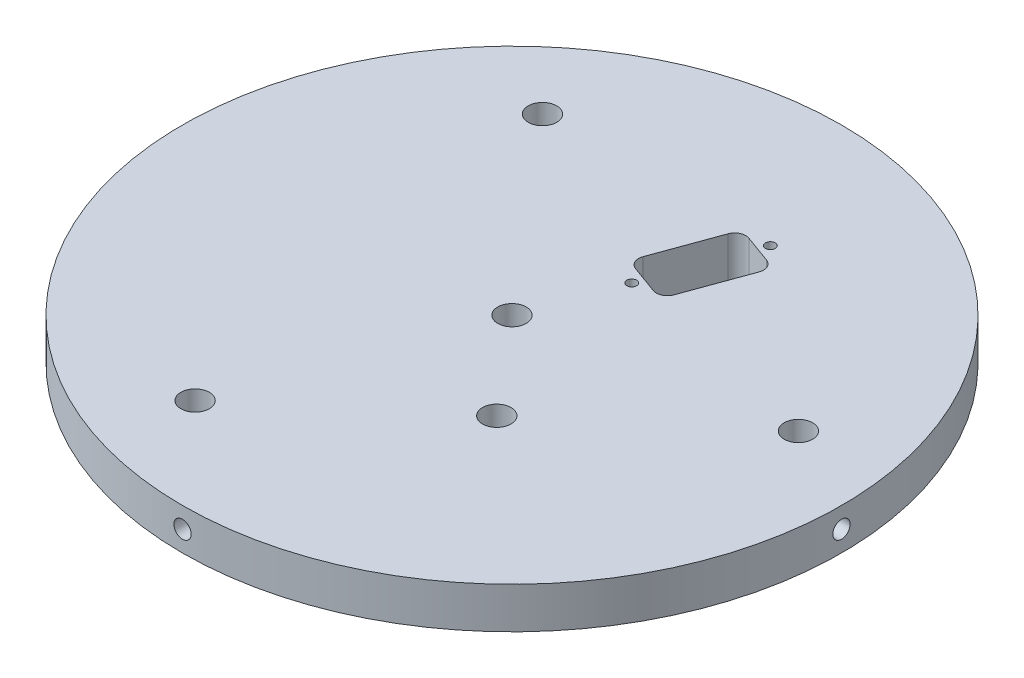
SolidWorks part; units mm, degrees
material "6061-T6 (SS)"
ref_plane "Front Plane" through (0, 0, 0) normal (0, 0, 1) x (1, 0, 0)
ref_plane "Top Plane" through (0, 0, 0) normal (0, 1, 0) x (1, 0, 0)
ref_plane "Right Plane" through (0, 0, 0) normal (1, 0, 0) x (0, 0, -1)
sketch "Sketch1" plane through (0, 0, 0) normal (0, 1, 0) x (1, 0, 0)
  line L0 (0, 0) -> (-50.3682, 60.0265)
  line L1 (0, 0) -> (50.3682, 60.0265)
  line L2 (0, 0) -> (0, 72.1431) construction
  circle A0 centre (0, 0) radius 78.359
  circle A1 centre (0, 0) radius 76.1746
  circle A2 centre (0, 0) radius 76.1746
  dimension "D1" = 156.718
  dimension "D2" = 152.3492
  dimension "D3" = 152.3492
  dimension "D4" = 80
extrude "Boss-Extrude1" add sketch "Sketch1" along normal blind 25.4 contours L2 A2 L1 A0 | L2 A1 L1 A2 | L2 A2 L1 A1 | L2 A0 L1 A2 | A2 L2 A1 L0 | A0 L2 A2 L0 | A2 L2 A0 L0 | A1 L2 A2 L0 region at (0, 0, 13.3592) region at (-23.5316, 0, -29.974) region at (-33.0764, 0, 70.9325) region at (-48.8794, 0, -59.85)
ref_plane "Plane1" through (0, 12.7, 0) normal (0, 1, 0) x (1, 0, 0)
sketch "Sketch6" plane through (0, 25.4, 0) normal (0, 1, 0) x (1, 0, 0)
  circle A0 centre (0, 0) radius 76.1746
  dimension "D1" = 152.3492
extrude "Boss-Extrude5" add sketch "Sketch6" along normal blind 9.525
sketch "Sketch7" plane through (0, 0, 0) normal (0, -1, 0) x (1, 0, 0)
  circle A0 centre (0, 0) radius 76.1746
  dimension "D1" = 152.3492
extrude "Boss-Extrude6" add sketch "Sketch7" along normal blind 9.525
sketch "Sketch8" plane through (0, -9.525, 0) normal (0, -1, 0) x (1, 0, 0)
  circle A0 centre (0, 0) radius 73.025
  dimension "D1" = 146.05
extrude "Cut-Extrude5" cut sketch "Sketch8" against normal up to surface (34.925 mm away) up to face at (0, 25.4, 76.1746)
ref_plane "Plane2" through (0, 0, -76.1746) normal (0, 0, -1) x (-1, 0, 0)
ref_plane "Plane5" through (0, 25.4, 0) normal (0, 1, 0) x (1, 0, 0)
ref_axis "Axis1" through (0, 0, 0) along (0, 1, 0)
sketch "Sketch3" plane through (0, 0, -76.1746) normal (0, 0, -1) x (-1, 0, 0)
  line L4 (76.1746, 0) -> (-76.1746, 0)
  line L5 (-76.1746, -9.525) -> (76.1746, -9.525)
  line L6 (76.1746, 25.4) -> (-76.1746, 25.4)
  line L7 (76.1746, 34.925) -> (-76.1746, 34.925)
  line L8 (0, 34.925) -> (0, 25.4) construction
  line L9 (0, 0) -> (0, -9.525) construction
  circle A0 centre (0, 30.1625) radius 2
  circle A1 centre (0, -4.7625) radius 2
  point P12 (0, 30.1625)
  point P13 (0, -4.7625)
  point P14 (-77.5445, 179.1871)
  dimension "D1" = 4
extrude "Cut-Extrude2" cut sketch "Sketch3" against normal blind 9.525 contours L8 A0 | L8 A0 | L9 A1 | L9 A1 region at (0, 30.1625, -76.1746) region at (0, -4.7625, -76.1746)
extrude "Cut-Extrude3" cut sketch "Sketch1<7>" against normal blind 9.525 from surface contours L2 A1 L1 A2 | A1 L2 A2 L0 | A2 L2 A0 L0 | L2 A2 L1 A0 region at (-23.5316, 0, -29.974) region at (-48.8794, 0, -59.85) starting at plane "Plane5"
sketch "Sketch1<7>" plane through (0, 0, 0) normal (0, 1, 0) x (1, 0, 0) same geometry as "Sketch1"
pattern_circular "CirPattern2" count 3 over 360 about axis through (0, 0, 0) along (0, 1, 0) of "Cut-Extrude3"
ref_plane "Plane3" through (0, 34.925, 0) normal (0, 1, 0) x (1, 0, 0)
sketch "Sketch4" plane through (0, 34.925, 0) normal (0, 1, 0) x (1, 0, 0)
  circle A0 centre (0, 0) radius 73.025
  dimension "D1" = 146.05
extrude "Boss-Extrude4" add sketch "Sketch4" against normal blind 9.525
pattern_circular "CirPattern3" count 4 over 360 about axis through (0, 0, 0) along (0, 1, 0) of "Cut-Extrude2"
sketch "Sketch9" plane through (0, 34.925, 0) normal (0, 1, 0) x (1, 0, 0)
  line L0 (0, 0) -> (-26.8004, -73.6334) construction
  line L1 (0, 0) -> (32.0596, -38.2071) construction
  circle A0 centre (0, 0) radius 3.3
  circle A1 centre (-19.5465, -53.7034) radius 3.3
  circle A2 centre (-36.7353, 43.7794) radius 3.3
  circle A3 centre (56.2818, 9.924) radius 3.3
  circle A4 centre (18.3677, -21.8897) radius 3.3
  point P15 (0, 0)
  dimension "D1" = 6.6
  dimension "D2" = 6.6
  dimension "D6" = 6.6
  dimension "D3" = 57.15
  dimension "D4" = 60
  dimension "D7" = 28.575
  dimension "D5" = 3
extrude "Cut-Extrude6" cut sketch "Sketch9" against normal through all
sketch "Sketch10" plane through (0, 25.4, 0) normal (0, 1, 0) x (1, 0, 0)
  circle A0 centre (0, 0) radius 82.3228
extrude "Cut-Extrude7" cut sketch "Sketch10" against normal through all
hole_wizard "Tap Drill for #4-40 Tap1" positions "Sketch12" profile "Sketch13" hole size "#4-40" standard "ANSI Inch" end condition through all
sketch "Sketch12" plane through (0, 34.925, 0) normal (0, 1, 0) x (1, 0, 0)
  line L0 (0, 0) -> (18.6243, 51.1699) construction
  line L2 (0, 0) -> (-36.7353, 43.7794) construction
  circle A0 centre (0, 0) radius 21.59 construction
  point P0 (7.3842, 20.288)
  point P2 (15.9347, 43.7803)
  dimension "D3" = 43.18
  dimension "D1" = 60
  dimension "D2" = 25
sketch "Sketch13" plane through (7.3842, 34.925, -20.288) normal (1, 0, 0) x (0, 0, 1)
  line L0 (0, 0) -> (0, 9.525)
  line L1 (0, 9.525) -> (1.1303, 9.525)
  line L2 (1.1303, 9.525) -> (1.1303, 0)
  line L5 (1.1303, 0) -> (0, 0)
  line L11 (0, -6.35) -> (0, 107.95) construction
  dimension "Thru Hole Dia." = 2.2606
  dimension "Thru Hole Depth" = 9.525
sketch "Sketch14" plane through (0, 34.925, 0) normal (0, 1, 0) x (1, 0, 0)
  line L0 (7.3842, 20.288) -> (15.9347, 43.7803) construction
  line L1 (14.6438, 22.7814) -> (19.8932, 37.2038)
  line L2 (11.3883, 21.2633) -> (4.9439, 23.6089)
  line L3 (18.3751, 40.4594) -> (11.9307, 42.8049)
  line L4 (3.4258, 26.8644) -> (8.6751, 41.2868)
  arc A0 (19.8932, 37.2038) -> (18.3751, 40.4594) centre (17.5063, 38.0725) ccw
  arc A1 (11.9307, 42.8049) -> (8.6751, 41.2868) centre (11.0619, 40.4181) ccw
  arc A2 (11.3883, 21.2633) -> (14.6438, 22.7814) centre (12.257, 23.6501) ccw
  arc A3 (4.9439, 23.6089) -> (3.4258, 26.8644) centre (5.8126, 25.9957) cw
  point P0 (8.1661, 22.4361)
  dimension "D4" = 2.54
  dimension "D5" = 2.54
  dimension "D1" = 2.286
  dimension "D2" = 2.286
  dimension "D3" = 11.938
extrude "Cut-Extrude9" cut sketch "Sketch14" against normal through all
equation "\"AB_Coupler_OD_Length\"= 1in"
equation "\"AB_Coupling_Section_Length\"= 0.375in"
equation "\"AB_Coupler_Length\"= \"AB_Coupler_OD_Length\" + \"AB_Coupling_Section_Length\" * 2"
equation "\"Cutout_Angle\" = 80"
equation "\"AB_Coupler_Num_Screws\"= 6"
equation "\"Num_Cutouts\" = 3"
equation "\"AB_Coupler_OD\"= 6.17in"
equation "\"AB_Coupler_ID\"= 5.75in"
equation "\"AB_Coupler_Surface_Diameter\"= 5.998in"
equation "\"D2@Sketch1\"=\"Bodytube_ID\""
equation "\"AB_Coupling_Screw_Diameter\"= 0.1065in"
equation "\"Aft_Section_Length\"= 39in"
equation "\"Aft_Lower_Length\"= 22in"
equation "\"Aft_Upper_Length\"= \"Aft_Section_Length\" - \"Aft_Lower_Length\" - \"AB_Coupler_OD_Length\""
equation "\"Mid_Coupler_Length\"= 13in"
equation "\"Lead_Screw_Dist\" = 2.25in"
equation "\"Lead_Screw_Diam\" = 11mm"
equation "\"Lead_Screw_Length\" = (\"Mid_Coupler_Length\" + 2*0.375in + 2*0.5in)"
equation "\"Bodytube_OD\" = 6.17in"
equation "\"Paddle_Pin_Offset\" = .25in"
equation "\"Bodytube_ID\" = 5.998in"
equation "\"Paddle_Pin_Radius\" = 2.25in"
equation "\"D1@Sketch4\"=\"AB_Coupler_ID\""
equation "\"D1@Sketch6\"=\"AB_Coupler_Surface_Diameter\""
equation "\"D1@Boss-Extrude5\"=\"AB_Coupling_Section_Length\""
equation "\"D1@Sketch7\"=\"AB_Coupler_Surface_Diameter\""
equation "\"D1@Boss-Extrude6\"=\"AB_Coupling_Section_Length\""
equation "\"D1@Sketch8\"=\"AB_Coupler_ID\""
equation "\"D3@Sketch9\"=\"Paddle_Pin_Radius\""
equation "\"Motor_OD\" = 4in"
equation "\"Fwd_Tube_Length\" = 40in"
equation "\"Mid_Tube_Length\" = 1in"
equation "\"AB_Paddle_Height\" = 0.375in"
equation "\"AB_Central_Bushing_Length\" = .75in"
equation "\"Paddle_Gear_OD\" = 3.2in"
equation "\"Fwd_BKHD_From_Top\" = 18in"
equation "\"Fin_Thickness\"= .118in"
equation "\"Guiderail_Cutout_Diameter\"= 1.5in"
equation "\"DB9_Hole_Dist\" = 25mm"
equation "\"D2@Sketch12\"=\"DB9_Hole_Dist\""
equation "\"Drive_Gear_OD\" = 1.7in"
equation "\"D3@Sketch12\"=\"Drive_Gear_OD\""
